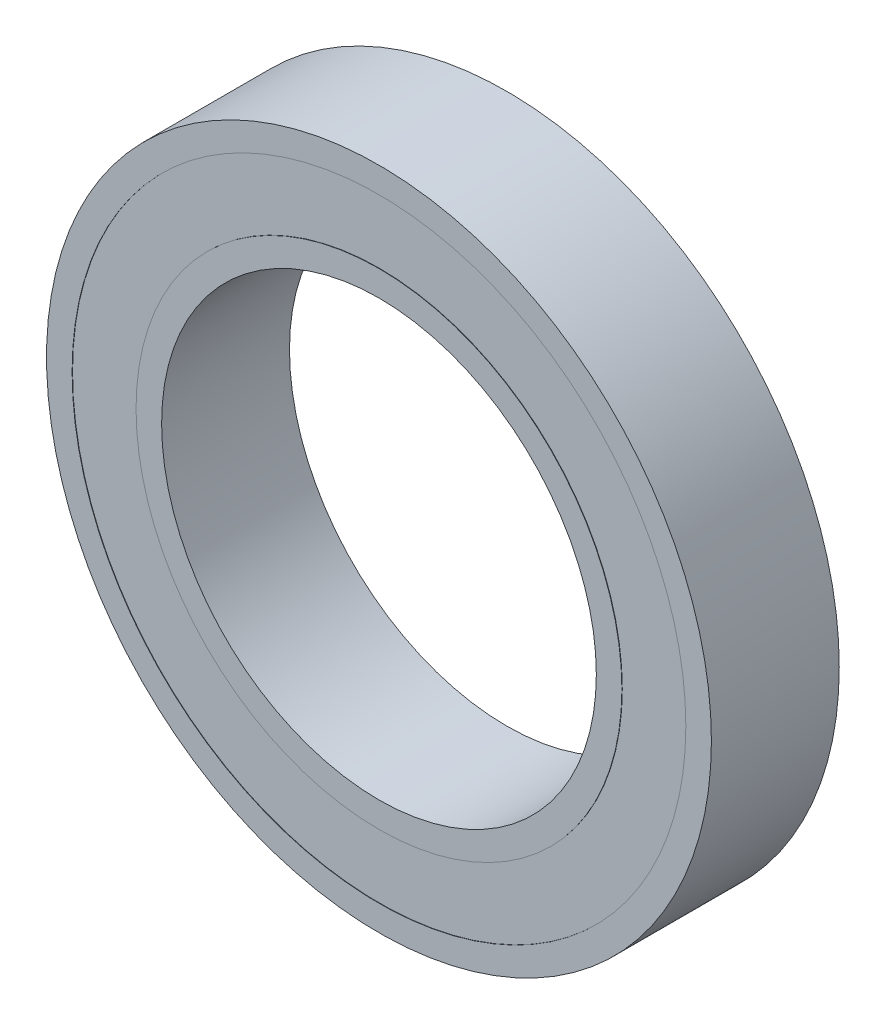
SolidWorks part; units mm, degrees
material "Chrome Stainless Steel"
ref_plane "Front Plane" through (0, 0, 0) normal (0, 0, 1) x (1, 0, 0)
ref_plane "Top Plane" through (0, 0, 0) normal (0, 1, 0) x (1, 0, 0)
ref_plane "Right Plane" through (0, 0, 0) normal (1, 0, 0) x (0, 0, -1)
sketch "Sketch1" plane through (0, 0, 0) normal (0, 0, 1) x (1, 0, 0)
  circle A0 centre (0, 0) radius 8.5
  circle A1 centre (0, 0) radius 9.5
  circle A2 centre (0, 0) radius 13
  circle A3 centre (0, 0) radius 12
  dimension "D1" = 26
  dimension "D2" = 17
  dimension "D3" = 19
  dimension "D4" = 24
extrude "Boss-Extrude1" add sketch "Sketch1" along normal blind 2.5 and the other way blind 2.5 contours A2 A3 | A1 A0 region at (-9.2313, 0, 0) region at (-12.6323, 0, 0)
extrude "Boss-Extrude2" add sketch "Sketch1<3>" along normal blind 2.4844 and the other way blind 2.4844 contours A3 A1 region at (-11.6606, 0, 0)
sketch "Sketch1<3>" plane through (0, 0, 0) normal (0, 0, 1) x (1, 0, 0) same geometry as "Sketch1"
equation "\"D1@Boss-Extrude2\"=2.5mm-1/64"
equation "\"D2@Boss-Extrude2\"=2.5mm-1/64"
